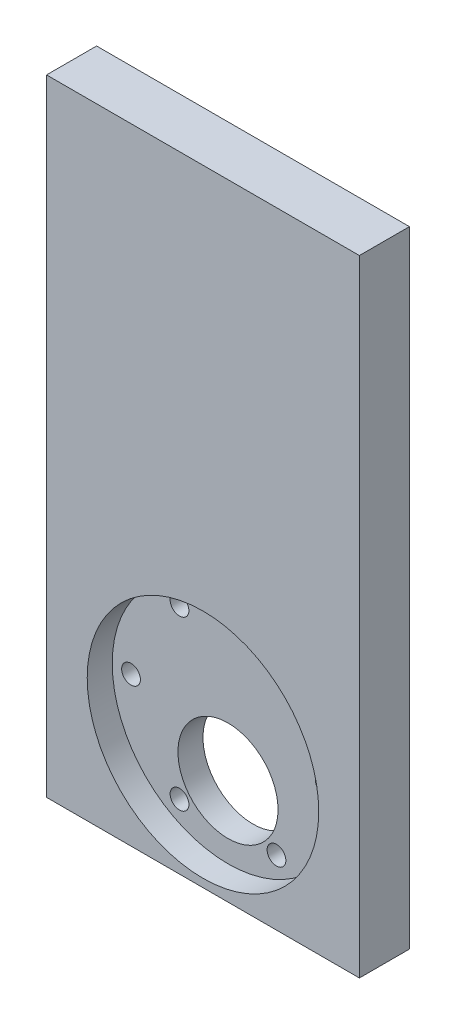
SolidWorks part; units mm, degrees
ref_plane "Front Plane" through (0, 0, 0) normal (0, 0, 1) x (1, 0, 0)
ref_plane "Top Plane" through (0, 0, 0) normal (0, 1, 0) x (1, 0, 0)
ref_plane "Right Plane" through (0, 0, 0) normal (1, 0, 0) x (0, 0, -1)
sketch "Sketch3" plane through (0, 0, 0) normal (0, 0, 1) x (1, 0, 0)
  line L0 (0, -7.5674) -> (0, 92.4326) construction
  line L1 (-25, 100) -> (25, 100)
  line L2 (-25, 100) -> (-25, 0)
  line L3 (-25, 0) -> (25, 0)
  line L4 (25, 100) -> (25, 0)
  line L5 (-7.75, 33.2234) -> (7.75, 33.2234) construction
  line L6 (7.75, 33.2234) -> (15.5, 19.8) construction
  line L7 (15.5, 19.8) -> (7.75, 6.3766) construction
  line L8 (7.75, 6.3766) -> (-7.75, 6.3766) construction
  line L9 (-7.75, 6.3766) -> (-15.5, 19.8) construction
  line L10 (-15.5, 19.8) -> (-7.75, 33.2234) construction
  line L11 (0, 33.2234) -> (0, 12.8) construction
  circle A4 centre (0, 12.8) radius 8
  circle A5 centre (-7.75, 33.2234) radius 1.5
  circle A6 centre (7.75, 33.2234) radius 1.5
  circle A7 centre (-15.5, 19.8) radius 1.5
  circle A8 centre (-7.75, 6.3766) radius 1.5
  circle A9 centre (7.75, 6.3766) radius 1.5
  circle A10 centre (15.5, 19.8) radius 1.5
  point P4 (0, 0)
  dimension "D4" = 16
  dimension "D5" = 6.4234
  dimension "D1" = 100
  dimension "D2" = 50
  dimension "D3" = 12.8
extrude "Boss-Extrude1" add sketch "Sketch3" along normal blind 8 contours L2 L3 L4 L1
extrude "Cut-Extrude2" cut sketch "Sketch3<3>" along normal blind 10 contours A6 | A5 | A7 | A8 | A9 | A10 | A4
sketch "Sketch3<3>" plane through (0, 0, 0) normal (0, 0, 1) x (1, 0, 0) same geometry as "Sketch3"
sketch "Sketch4" plane through (0, 0, 8) normal (0, 0, 1) x (1, 0, 0)
  line L0 (-15.5, 19.8) -> (15.5, 19.8) construction
  circle A0 centre (0, 19.8) radius 18.5
  dimension "D1" = 37
extrude "Cut-Extrude3" cut sketch "Sketch4" against normal blind 4 contours A0
